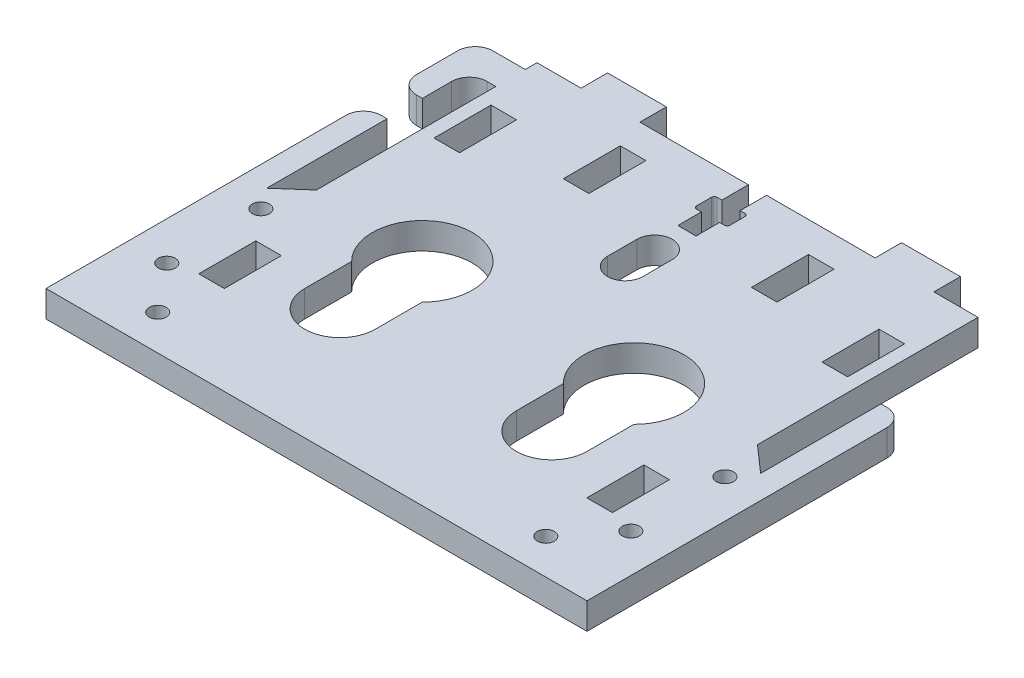
SolidWorks part; units mm, degrees
ref_plane "Front Plane" through (0, 0, 0) normal (0, 0, 1) x (1, 0, 0)
ref_plane "Top Plane" through (0, 0, 0) normal (0, 1, 0) x (1, 0, 0)
ref_plane "Right Plane" through (0, 0, 0) normal (1, 0, 0) x (0, 0, -1)
sketch "Sketch1" plane through (0, 0, 0) normal (0, 1, 0) x (1, 0, 0)
  line L1 (-37.5, 37.5) -> (37.5, 37.5)
  line L2 (-37.5, 37.5) -> (-37.5, -37.5)
  line L3 (-37.5, -37.5) -> (37.5, -37.5)
  line L4 (37.5, 37.5) -> (37.5, -37.5)
  line L5 (-37.5, 37.5) -> (37.5, -37.5) construction
  line L6 (-37.5, -37.5) -> (37.5, 37.5) construction
  point P0 (0, 0)
  dimension "D1" = 75
  dimension "D2" = 75
extrude "MainShape" add sketch "Sketch1" along normal blind 4.5
sketch "Sketch2" plane through (0, 4.5, 0) normal (0, 1, 0) x (1, 0, 0)
  line L0 (0, -37.5) -> (0, 37.5) construction
  line L1 (-37.5, -37.5) -> (37.5, -37.5) construction
  line L2 (37.5, 37.5) -> (-37.5, 37.5) construction
  line L4 (-5, 42) -> (5, 42)
  line L5 (-5, 42) -> (-5, 33)
  line L6 (-5, 33) -> (5, 33)
  line L7 (5, 42) -> (5, 33)
  line L8 (-5, 42) -> (5, 33) construction
  line L9 (-5, 33) -> (5, 42) construction
  dimension "D1" = 10
  dimension "D2" = 4.5
extrude "Tab1" [suppressed] add sketch "Sketch2" against normal through all
sketch "Sketch4" [suppressed] plane through (0, 4.5, 0) normal (0, 1, 0) x (1, 0, 0)
  line L0 (0, 42) -> (0, -37.5) construction
  line L1 (5, 42) -> (-5, 42) construction
  line L2 (-47.5, -37.5) -> (47.5, -37.5) construction
  line L3 (-40, 37.5) -> (-40, 27) construction
  line L4 (-5, 37.5) -> (-47.5, 37.5) construction
  line L5 (-38.25, 27) -> (-41.75, 27) construction
  line L6 (-41.75, 27) -> (-41.75, 37.5) construction
  line L7 (-38.25, 27) -> (-41.75, 27)
  line L8 (-41.75, 27) -> (-41.75, 29.5)
  line L9 (-41.75, 29.5) -> (-42.75, 29.5)
  line L10 (-43, 29.75) -> (-43, 33.45)
  line L11 (-42.75, 33.7) -> (-41.75, 33.7)
  line L12 (-41.75, 33.7) -> (-41.75, 37.5)
  line L13 (-41.75, 37.5) -> (-38.25, 37.5)
  line L14 (-38.25, 27) -> (-38.25, 37.5) construction
  line L15 (-38.25, 33.7) -> (-38.25, 37.5)
  line L16 (-37.25, 33.7) -> (-38.25, 33.7)
  line L17 (-37, 29.75) -> (-37, 33.45)
  line L18 (-38.25, 29.5) -> (-37.25, 29.5)
  line L19 (-38.25, 27) -> (-38.25, 29.5)
  line L20 (38.25, 27) -> (38.25, 37.5) construction
  line L21 (41.75, 27) -> (41.75, 37.5) construction
  line L22 (38.25, 27) -> (41.75, 27) construction
  line L23 (40, 37.5) -> (40, 27) construction
  line L24 (38.25, 27) -> (38.25, 29.5)
  line L25 (38.25, 29.5) -> (37.25, 29.5)
  line L26 (37, 29.75) -> (37, 33.45)
  line L27 (37.25, 33.7) -> (38.25, 33.7)
  line L28 (38.25, 33.7) -> (38.25, 37.5)
  line L29 (41.75, 37.5) -> (38.25, 37.5)
  line L30 (41.75, 33.7) -> (41.75, 37.5)
  line L31 (42.75, 33.7) -> (41.75, 33.7)
  line L32 (43, 29.75) -> (43, 33.45)
  line L33 (41.75, 29.5) -> (42.75, 29.5)
  line L34 (41.75, 27) -> (41.75, 29.5)
  line L35 (38.25, 27) -> (41.75, 27)
  arc A0 (-42.75, 29.5) -> (-43, 29.75) centre (-42.75, 29.75) cw
  arc A1 (-37, 29.75) -> (-37.25, 29.5) centre (-37.25, 29.75) cw
  arc A2 (-37.25, 33.7) -> (-37, 33.45) centre (-37.25, 33.45) cw
  arc A3 (-43, 33.45) -> (-42.75, 33.7) centre (-42.75, 33.45) cw
  arc A4 (43, 33.45) -> (42.75, 33.7) centre (42.75, 33.45) ccw
  arc A5 (37.25, 33.7) -> (37, 33.45) centre (37.25, 33.45) ccw
  arc A6 (37, 29.75) -> (37.25, 29.5) centre (37.25, 29.75) ccw
  arc A7 (42.75, 29.5) -> (43, 29.75) centre (42.75, 29.75) ccw
  point P24 (-43, 29.5)
  point P27 (-37, 29.5)
  point P30 (-37, 33.7)
  point P33 (-43, 33.7)
  point P56 (43, 33.7)
  point P57 (37, 33.7)
  point P58 (37, 29.5)
  point P59 (43, 29.5)
  dimension "D7" = 0.5
  dimension "D1" = 11
  dimension "D2" = 1.55
  dimension "D3" = 3.5
  dimension "D4" = 2.85
  dimension "D5" = 8
  dimension "D6" = 40
extrude "Cut-Extrude2" [suppressed] cut sketch "Sketch4" against normal through all
sketch "Sketch5" plane through (0, 4.5, 0) normal (0, 1, 0) x (1, 0, 0)
  line L0 (0, -37.5) -> (0, 37.5) construction
  line L1 (-37.5, -37.5) -> (37.5, -37.5) construction
  line L3 (33, 37.5) -> (33, -37.5) construction
  line L4 (37.5, 37.5) -> (-37.5, 37.5) construction
  line L5 (-33, 37.5) -> (-33, -37.5) construction
  line L6 (30.825, 27.35) -> (35.175, 27.35)
  line L7 (30.825, 27.35) -> (30.825, 17.65)
  line L8 (30.825, 17.65) -> (35.175, 17.65)
  line L9 (35.175, 27.35) -> (35.175, 17.65)
  line L10 (30.825, 27.35) -> (35.175, 17.65) construction
  line L11 (30.825, 17.65) -> (35.175, 27.35) construction
  line L12 (-30.825, 17.65) -> (-35.175, 27.35) construction
  line L13 (-30.825, 27.35) -> (-35.175, 17.65) construction
  line L14 (-35.175, 27.35) -> (-35.175, 17.65)
  line L15 (-30.825, 17.65) -> (-35.175, 17.65)
  line L16 (-30.825, 27.35) -> (-30.825, 17.65)
  line L17 (-30.825, 27.35) -> (-35.175, 27.35)
  line L18 (-37.5, 2.5) -> (37.5, 2.5) construction
  line L19 (-37.5, 37.5) -> (-37.5, -37.5) construction
  line L20 (37.5, -37.5) -> (37.5, 37.5) construction
  line L21 (-30.825, -22.35) -> (-35.175, -12.65) construction
  line L22 (-30.825, -12.65) -> (-35.175, -22.35) construction
  line L23 (30.825, -12.65) -> (35.175, -22.35) construction
  line L24 (30.825, -22.35) -> (35.175, -12.65) construction
  line L25 (-30.825, -22.35) -> (-35.175, -22.35)
  line L26 (-30.825, -22.35) -> (-30.825, -12.65)
  line L27 (-30.825, -12.65) -> (-35.175, -12.65)
  line L28 (-35.175, -22.35) -> (-35.175, -12.65)
  line L29 (35.175, -22.35) -> (35.175, -12.65)
  line L30 (30.825, -12.65) -> (35.175, -12.65)
  line L31 (30.825, -22.35) -> (30.825, -12.65)
  line L32 (30.825, -22.35) -> (35.175, -22.35)
  line L33 (-30.825, 27.35) -> (-35.175, 17.65) construction
  line L34 (-37.5, 37.5) -> (37.5, 37.5) construction
  line L35 (37.5, 37.5) -> (-37.5, 37.5) construction
  point P10 (33, 22.5)
  point P21 (-33, 22.5)
  point P36 (-33, -17.5)
  point P37 (33, -17.5)
  dimension "D1" = 33
  dimension "D2" = 9.7
  dimension "D3" = 4.35
  dimension "D4" = 15
  dimension "D5" = 40
extrude "Cut-Extrude3" cut sketch "Sketch5" against normal through all
sketch "Sketch6" plane through (0, 4.5, 0) normal (0, 1, 0) x (1, 0, 0)
  line L0 (-18, -37.5) -> (-18, 28) construction
  line L1 (-24, -15.5) -> (-24, -7.5208)
  line L3 (-37.5, -15.5) -> (37.5, -15.5) construction
  line L4 (-37.5, 37.5) -> (-37.5, -37.5) construction
  line L5 (37.5, -37.5) -> (37.5, 37.5) construction
  line L6 (37.5, 37.5) -> (-37.5, 37.5) construction
  line L7 (-37.5, -37.5) -> (37.5, -37.5) construction
  line L8 (-12, -15.5) -> (-12, -7.5208)
  line L9 (-37.5, 37.5) -> (37.5, 37.5) construction
  arc A0 (-24, -15.5) -> (-12, -15.5) centre (-18, -15.5) ccw
  arc A2 (-12, -7.5208) -> (-24, -7.5208) centre (-18, -1.5) ccw
  dimension "D1" = 12
  dimension "D6" = 8.5
  dimension "D2" = 53
  dimension "D3" = 0
  dimension "D5" = 0
  dimension "D7" = 14
  dimension "D4" = 18
extrude "Cut-Extrude4" cut sketch "Sketch6" against normal through all
sketch "Sketch13" plane through (0, 4.5, 0) normal (0, 1, 0) x (1, 0, 0)
  line L0 (-37.5, 0) -> (-46, -7.5)
  line L1 (-37.5, 37.5) -> (-37.5, -37.5) construction
  line L2 (-46, -7.5) -> (-46, -37.5)
  line L3 (-46, -37.5) -> (-37.5, -37.5)
  line L4 (-37.5, -37.5) -> (-37.5, 0)
  line L5 (0, 37.5) -> (0, -37.5) construction
  line L6 (37.5, 37.5) -> (-37.5, 37.5) construction
  line L7 (-37.5, -37.5) -> (37.5, -37.5) construction
  line L8 (37.5, -37.5) -> (37.5, 0)
  line L9 (46, -37.5) -> (37.5, -37.5)
  line L10 (46, -7.5) -> (46, -37.5)
  line L11 (37.5, 0) -> (46, -7.5)
  line L12 (-37.5, -37.5) -> (-37.5, 0)
  line M23 (37.5, -37.5) -> (37.5, 37.5)
  line M25 (-37.5, 37.5) -> (-37.5, -37.5)
  dimension "D1" = 46
  dimension "D2" = 30
extrude "Boss-Extrude2" add sketch "Sketch13" against normal through all contours L2 L3 L0 M25 | L11 L9 L10 M23 region at (-41.5926, 4.5, 20.5556) region at (41.5926, 4.5, 20.5556)
sketch "Sketch8" plane through (0, 4.5, 0) normal (0, 1, 0) x (1, 0, 0)
  line L0 (-18, -9.5) -> (-18, -21.5) construction
  line L1 (-18, -15.5) -> (-39.46, -15.5) construction
  line L2 (-39.46, -23.5) -> (-39.46, -7.5) construction
  line L3 (-18, -21.5) -> (-18, -9.5) construction
  circle A0 centre (-39.46, -7.5) radius 1.45
  circle A1 centre (-18, -15.5) radius 6 construction
  circle A2 centre (-39.46, -23.5) radius 1.45
  dimension "D3" = 2.9
  dimension "D1" = 0
  dimension "D2" = 8
  dimension "D4" = 21.46
extrude "Cut-Extrude6" cut sketch "Sketch8" against normal through all
mirror "Mirror1" about plane through (0, 0, 0) normal (1, 0, 0) of "Cut-Extrude6", "Cut-Extrude4"
sketch "Sketch11" plane through (0, 4.5, 0) normal (0, 1, 0) x (1, 0, 0)
  line L0 (0, 37.5) -> (0, -37.5) construction
  line L1 (37.5, 37.5) -> (-37.5, 37.5) construction
  line L2 (-46, -37.5) -> (46, -37.5) construction
  line L3 (-25, 42) -> (-25, 37.5) construction
  line L4 (-30, 37.5) -> (-20, 37.5)
  line L5 (-30, 37.5) -> (-30, 42)
  line L6 (-30, 42) -> (-20, 42)
  line L7 (-20, 37.5) -> (-20, 42)
  line L8 (25, 42) -> (25, 37.5) construction
  line L9 (20, 37.5) -> (20, 42)
  line L10 (30, 42) -> (20, 42)
  line L11 (30, 37.5) -> (30, 42)
  line L12 (30, 37.5) -> (20, 37.5)
  dimension "D1" = 10
  dimension "D2" = 4.5
  dimension "D3" = 25
extrude "RearTabs" add sketch "Sketch11" against normal through all
sketch "Sketch12" plane through (0, 4.5, 0) normal (0, 1, 0) x (1, 0, 0)
  line L0 (0, 0) -> (0, 37.5) construction
  line L1 (20, 37.5) -> (-20, 37.5) construction
  line L2 (1.55, 37.5) -> (-1.55, 37.5)
  line L3 (-1.55, 37.5) -> (-1.55, 33)
  line L4 (-1.55, 33) -> (-2.35, 33)
  line L5 (-2.85, 32.5) -> (-2.85, 30)
  line L6 (-2.35, 29.5) -> (-1.55, 29.5)
  line L7 (-1.55, 29.5) -> (-1.55, 25.5)
  line L8 (-1.55, 25.5) -> (1.55, 25.5)
  line L9 (1.55, 29.5) -> (1.55, 25.5)
  line L10 (2.35, 29.5) -> (1.55, 29.5)
  line L11 (2.85, 32.5) -> (2.85, 30)
  line L12 (1.55, 33) -> (2.35, 33)
  line L13 (1.55, 37.5) -> (1.55, 33)
  arc A0 (-2.85, 30) -> (-2.35, 29.5) centre (-2.35, 30) ccw
  arc A1 (-2.35, 33) -> (-2.85, 32.5) centre (-2.35, 32.5) ccw
  arc A2 (2.35, 33) -> (2.85, 32.5) centre (2.35, 32.5) cw
  arc A3 (2.85, 30) -> (2.35, 29.5) centre (2.35, 30) cw
  point P14 (-2.85, 29.5)
  point P17 (-2.85, 33)
  point P25 (0, 25.5)
  point P28 (2.85, 33)
  point P29 (2.85, 29.5)
  dimension "D5" = 8
  dimension "D1" = 12
  dimension "D6" = 0.5
  dimension "D2" = 3.5
  dimension "D3" = 2.85
  dimension "D4" = 1.55
extrude "FrontScrewSlot" cut sketch "Sketch12" against normal through all
sketch "Sketch14" plane through (0, 4.5, 0) normal (0, 1, 0) x (1, 0, 0)
  line L0 (-33, 27.35) -> (-33, -37.5) construction
  line L1 (-30.825, 27.35) -> (-35.175, 27.35) construction
  line L2 (-46, -37.5) -> (46, -37.5) construction
  line L3 (-30, 37.5) -> (-37.5, 37.5) construction
  line L4 (0, 0) -> (0, -37.5) construction
  line L5 (33, 27.35) -> (33, -37.5) construction
  line L6 (-33, 27.35) -> (-33, -37.5) construction
  circle A0 centre (-33, -31.5) radius 1.45
  circle A1 centre (33, -31.5) radius 1.45
  dimension "D2" = 2.9
  dimension "D1" = 69
extrude "BraceScrews" cut sketch "Sketch14" against normal through all
sketch "Sketch15" plane through (0, 4.5, 0) normal (0, 1, 0) x (1, 0, 0)
  line L0 (0, -37.5) -> (0, 25.5) construction
  line L1 (-46, -37.5) -> (46, -37.5) construction
  line L2 (-1.55, 25.5) -> (1.55, 25.5) construction
  line L3 (16, 27.5) -> (-16, 27.5) construction
  line L4 (-1.55, 37.5) -> (-20, 37.5) construction
  line L5 (-18.175, 32.35) -> (-13.825, 32.35)
  line L6 (-18.175, 32.35) -> (-18.175, 22.65)
  line L7 (-18.175, 22.65) -> (-13.825, 22.65)
  line L8 (-13.825, 32.35) -> (-13.825, 22.65)
  line L9 (-18.175, 32.35) -> (-13.825, 22.65) construction
  line L10 (-18.175, 22.65) -> (-13.825, 32.35) construction
  line L11 (18.175, 22.65) -> (13.825, 32.35) construction
  line L12 (18.175, 32.35) -> (13.825, 22.65) construction
  line L13 (13.825, 32.35) -> (13.825, 22.65)
  line L14 (18.175, 22.65) -> (13.825, 22.65)
  line L15 (18.175, 32.35) -> (18.175, 22.65)
  line L16 (18.175, 32.35) -> (13.825, 32.35)
  point P19 (0, 27.5)
  dimension "D1" = 16
  dimension "D2" = 4.35
  dimension "D3" = 9.7
  dimension "D4" = 10
extrude "FanTabs" cut sketch "Sketch15" against normal through all
sketch "Sketch16" plane through (0, 4.5, 0) normal (0, 1, 0) x (1, 0, 0)
  line L0 (0, 0) -> (0, 25.5) construction
  line L1 (-1.55, 25.5) -> (1.55, 25.5) construction
  line L2 (0, 20) -> (0, 15) construction
  line L3 (3, 20) -> (3, 15)
  line L4 (-3, 20) -> (-3, 15)
  arc A0 (3, 20) -> (-3, 20) centre (0, 20) ccw
  arc A1 (-3, 15) -> (3, 15) centre (0, 15) ccw
  point P7 (0, 17.5)
  dimension "D1" = 3
  dimension "D2" = 20
  dimension "D3" = 5
extrude "WiringSlot" cut sketch "Sketch16" against normal through all
sketch "Sketch17" [suppressed] plane through (0, 4.5, 0) normal (0, 1, 0) x (1, 0, 0)
  line L0 (-37.5, 14.5) -> (-37.5, 10.5) construction
  line L3 (-37.5, 37.5) -> (-37.5, 0) construction
  line L4 (-36, 14.5) -> (-36, 10.5)
  line L5 (-39, 14.5) -> (-39, 10.5)
  line L6 (-37.5, 14.5) -> (-37.5, 10.5) construction
  line L7 (-34, 14.5) -> (-34, 10.5)
  line L8 (-41, 14.5) -> (-41, 10.5)
  line L9 (-41, 12.5) -> (-37.5, 12.5) construction
  line L10 (0, 0) -> (0, -12.1805) construction
  arc A0 (-36, 14.5) -> (-39, 14.5) centre (-37.5, 14.5) ccw
  arc A1 (-39, 10.5) -> (-36, 10.5) centre (-37.5, 10.5) ccw
  arc A2 (-34, 14.5) -> (-41, 14.5) centre (-37.5, 14.5) ccw
  arc A3 (-41, 10.5) -> (-34, 10.5) centre (-37.5, 10.5) ccw
  point P4 (-37.5, 12.5)
  point P10 (-37.5, 12.5)
  dimension "D4" = 4
  dimension "D5" = 25
  dimension "D1" = 0
  dimension "D2" = 2
  dimension "D3" = 1.5
extrude "Boss-Extrude3" [suppressed] add sketch "Sketch17" against normal through all
mirror "Mirror2" [suppressed] about plane through (0, 0, 0) normal (1, 0, 0)
sketch "Sketch18" [suppressed] plane through (0, 4.5, 0) normal (0, 1, 0) x (1, 0, 0)
  line L0 (0, -37.5) -> (0, 47.6111) construction
  line L1 (-45, -37.5) -> (45, -37.5) construction
  line L2 (-12, 2) -> (-12, -19.46) construction
  line L3 (-4, -19.46) -> (-20, -19.46) construction
  circle A0 centre (-12, 2) radius 5
  circle A1 centre (-20, -19.46) radius 1.45
  circle A2 centre (-4, -19.46) radius 1.45
  dimension "D2" = 8
  dimension "D4" = 21.46
  dimension "D1" = 2.9
  dimension "D3" = 10
  dimension "D5" = 12
  dimension "D6" = 2
extrude "Cut-Extrude7" [suppressed] cut sketch "Sketch18" against normal through all
mirror "Mirror3" [suppressed] about plane through (0, 0, 0) normal (1, 0, 0)
sketch "Sketch19" [suppressed] plane through (0, 4.5, 0) normal (0, 1, 0) x (1, 0, 0)
  line L0 (-17, 2) -> (-7, 2) construction
  line L1 (-12, 2) -> (-4, 2) construction
  line L2 (-12, 4) -> (-4, 4)
  line L3 (-12, 0) -> (-4, 0)
  line L4 (-12, 7) -> (-12, -3) construction
  line L5 (0, 0) -> (0, 6.8806) construction
  line L6 (12, 7) -> (12, -3) construction
  line L7 (17, 2) -> (7, 2) construction
  line L8 (12, 2) -> (4, 2) construction
  line L9 (12, 4) -> (4, 4)
  line L10 (12, 0) -> (4, 0)
  circle A0 centre (-12, 2) radius 5 construction
  arc A1 (-12, 4) -> (-12, 0) centre (-12, 2) ccw
  arc A2 (-4, 0) -> (-4, 4) centre (-4, 2) ccw
  arc A3 (12, 4) -> (12, 0) centre (12, 2) cw
  arc A4 (4, 0) -> (4, 4) centre (4, 2) cw
  point P6 (-8, 2)
  point P23 (8, 2)
  dimension "D1" = 2
  dimension "D2" = 8
extrude "Cut-Extrude8" [suppressed] cut sketch "Sketch19" against normal through all
sketch "Sketch20" plane through (0, 4.5, 0) normal (0, 1, 0) x (1, 0, 0)
  line L0 (0, 0) -> (0, -37.5) construction
  line L1 (-46, -37.5) -> (46, -37.5) construction
  line L2 (-26.9758, -32.9017) -> (-26.9758, -26.6196)
  line L3 (-26.9758, -26.6196) -> (-6.5592, -26.6196)
  line L4 (-6.5592, -26.6196) -> (-6.5592, 9.4097)
  line L5 (-6.5592, 9.4097) -> (6.5592, 9.4097)
  line L6 (-26.9758, -32.9017) -> (26.9758, -32.9017)
  line L7 (6.5592, -26.6196) -> (6.5592, 9.4097)
  line L8 (26.9758, -26.6196) -> (6.5592, -26.6196)
  line L9 (26.9758, -32.9017) -> (26.9758, -26.6196)
  point P12 (0, -32.9017)
  point P13 (0, 9.4097)
extrude "Cut-Extrude9" [suppressed] cut sketch "Sketch20" against normal through all
sketch "Sketch21" plane through (0, 4.5, 0) normal (0, 1, 0) x (1, 0, 0)
  line L0 (-46, -37.5) -> (-46, 35.5) construction
  line L1 (-37, 35.5) -> (-43, 35.5)
  line L4 (-46, 32.5) -> (-46, 25.5)
  line L5 (-43, 22.5) -> (-42, 22.5)
  line L6 (-42, 22.5) -> (-42, 27.5)
  line L7 (-39, 30.5) -> (-37, 30.5)
  line L9 (-37, 30.5) -> (-37, 35.5)
  line L10 (-30, 37.5) -> (-37.5, 37.5) construction
  line L11 (-37.5, 37.5) -> (-37.5, 0) construction
  arc A0 (-42, 27.5) -> (-39, 30.5) centre (-39, 27.5) cw
  arc A1 (-46, 25.5) -> (-43, 22.5) centre (-43, 25.5) ccw
  arc A2 (-43, 35.5) -> (-46, 32.5) centre (-43, 32.5) ccw
  point P19 (-46, 22.5)
  point P24 (-42, 37.5)
  dimension "D1" = 3
  dimension "D4" = 3
  dimension "D2" = 15
  dimension "D3" = 5
  dimension "D5" = 4
  dimension "D6" = 0.5
  dimension "D7" = 2
extrude "Boss-Extrude4" add sketch "Sketch21" against normal through all
sketch "Sketch22" plane through (0, 4.5, 0) normal (0, 1, 0) x (1, 0, 0)
  line L0 (-46, -7.5) -> (-46, 13.5)
  line L1 (-43, 16.5) -> (-42, 16.5)
  line L2 (-42, 16.5) -> (-42, -3.9706)
  line L3 (-37.5, 0) -> (-46, -7.5) construction
  line L4 (-42, -3.9706) -> (-46, -7.5)
  line L5 (-46, 16.5) -> (-46, 28.3122) construction
  line L6 (-46, 32.5) -> (-46, 25.5) construction
  line L7 (-42, 22.6875) -> (-42, 12.0504) construction
  line L8 (-42, 22.5) -> (-42, 27.5) construction
  arc A0 (-46, 13.5) -> (-43, 16.5) centre (-43, 13.5) cw
  dimension "D2" = 3
  dimension "D1" = 6
extrude "Boss-Extrude5" add sketch "Sketch22" against normal through all
mirror "Mirror6" about plane through (0, 0, 0) normal (1, 0, 0) of "Boss-Extrude5"
equation "\"X-ROD-SPACING\"=45"
equation "\"Y-ROD-SPACING\"=75"
equation "\"Z-ROD-SPACING\"=17.5"
equation "\"Y-BED-OFFSET\"=2"
equation "\"Y-BED-ROD-INSET\"=3.5"
equation "\"Y-BED-SCREW-SPACING\"=209"
equation "\"Y-BED-SCREW-CUTOUT-SLOT-HEIGHT\"=2"
equation "\"T-SLOT-NUT-FILLET-RADIUS\"=0.5"
equation "\"T-SLOT-SCREW-SHAFT-RADIUS\"=1.55"
equation "\"T-SLOT-SCREW-SHAFT-CUTOUT-LENGTH\"=11"
equation "\"T-SLOT-NUT-DEPTH\"=3.5"
equation "\"T-SLOT-NUT-WIDTH\"=2.85"
equation "\"T-SLOT-NUT-END-DISTANCE\"=8"
equation "\"ACRYLIC-THICKNESS\"=10"
equation "\"ACRYLIC-THICKNESS2\"=4.5"
equation "\"ACRYLIC-TAB-CUTOUT-SIZE\"=\"ACRYLIC-THICKNESS\"+\"ACRYLIC-TAB-TOLERANCE\"*2"
equation "\"ACRYLIC-TAB-WIDTH\"=\"ACRYLIC-THICKNESS\""
equation "\"ACRYLIC-M3-HOLE\"=2.9"
equation "\"SMOOTHROD-CAP-SCREW-DISTANCE\"=20"
equation "\"FRAME-WIDTH-INNER\"=370"
equation "\"NEMA17-HOLE-SPACING\"=31"
equation "\"NEMA17-CENTRAL-CUTOUT\"=22.5"
equation "\"Z-BRACKET-REACH\"=55"
equation "\"Z-ROD-INSET\"=13.5"
equation "\"TOP-BRACKET-SPACING\"=40"
equation "\"SMOOTHROD-X-LENGTH\"=350"
equation "\"SMOOTHROD-Y-LENGTH\"=350"
equation "\"SMOOTHROD-Z-LENGTH\"=350"
equation "\"SMOOTHROD-TIGHTENING-HEADROOM\"=.25"
equation "\"LEADSCREW-Z-LENGTH\"=300"
equation "\"SCREW-LENGTH-FRAME\"=\"ACRYLIC-THICKNESS\" + 10"
equation "\"SCREW-LENGTH-MOTOR\"=\"ACRYLIC-THICKNESS\" + 5"
equation "\"SCREW-LENGTH-EXTRUDER\"=28"
equation "\"SCREW-HEAD-RADIUS\"=6"
equation "\"PRINTED-X-SMOOTHROD-DIAMETER\"=8.8"
equation "\"PRINTED-X-SMOOTHROD-CUTOUT\"=10"
equation "\"PRINTED-X-BASE-HEIGHT\"=10"
equation "\"PRINTED-LM8UU-CUTOUT-SIZE\"=15.5"
equation "\"PRINTED-LM8UU-CUTOUT-LENGTH\"=24.5"
equation "\"PRINTED-X-IDLER-HEIGHT\"=16"
equation "\"PSU-MOUNTING-WIDTH\"=95"
equation "\"PSU-MOUNTING-HEIGHT\"=177"
equation "\"Y-BELT-TO-ROD-DISTANCE\"=20"
equation "\"SPOOL-HOLDER-ROD-SPACING\"=150"
equation "\"ACRYLIC-X-CARRIAGE-WIDTH\"=55"
equation "\"ACRYLIC-X-CARRIAGE-HEIGHT\"=75"
equation "\"ACRYLIC-X-CARRIAGE-SCREW-SPACING-X\"=15"
equation "\"ACRYLIC-X-CARRIAGE-SCREW-SPACING-Y\"=33"
equation "\"ACRYLIC-X-CARRIAGE-CENTER-TAB-SPACING\"=14"
equation "\"D1@MainShape\" = \"ACRYLIC-THICKNESS2\""
equation "\"D1@Sketch2\"=\"ACRYLIC-TAB-WIDTH\""
equation "\"D2@Sketch2\"=\"ACRYLIC-THICKNESS2\""
equation "\"D1@Sketch4\"=\"T-SLOT-SCREW-SHAFT-CUTOUT-LENGTH\""
equation "\"D2@Sketch4\"=\"T-SLOT-SCREW-SHAFT-RADIUS\""
equation "\"D3@Sketch4\"=\"T-SLOT-NUT-DEPTH\""
equation "\"D4@Sketch4\"=\"T-SLOT-NUT-WIDTH\""
equation "\"D5@Sketch4\"=\"T-SLOT-NUT-END-DISTANCE\""
equation "\"D7@Sketch4\"=\"T-SLOT-NUT-FILLET-RADIUS\""
equation "\"ACRYLIC-X-CARRIAGE-EXTRUDER-SHELF-DEPTH\"=\"ACRYLIC-X-CARRIAGE-EXTRUDER-OFFSET\" + 28"
equation "\"ACRYLIC-X-CARRIAGE-LM8UU-CUTOUT-WIDTH\"=24.25"
equation "\"ACRYLIC-X-CARRIAGE-EXTRUDER-BRACE-SPACING\"=23"
equation "\"ACRYLIC-X-CARRIAGE-EXTRUDER-BRACE-TAB-OFFSET\"=20"
equation "\"ACRYLIC-X-CARRIAGE-EXTRUDER-BRACE-HEIGHT\"=35"
equation "\"ACRYLIC-X-CARRIAGE-EXTRUDER-BRACE-SCREW-SPACING\"=22"
equation "\"D2@Sketch5\"=\"ACRYLIC-THICKNESS2-TAB-CUTOUT-HEIGHT\""
equation "\"D3@Sketch5\"=\"ACRYLIC-THICKNESS2-TAB-CUTOUT-WIDTH\""
equation "\"D3@Sketch8\"=\"ACRYLIC-M3-HOLE\""
equation "\"ACRYLIC-X-CARRIAGE-EXTRUDER-ANGLE\"=90"
equation "\"ACRYLIC-X-CARRIAGE-EXTRUDER-OFFSET\"=26"
equation "\"ACRYLIC-TAB-TOLERANCE\"=-.05"
equation "\"ACRYLIC-X-CARRIAGE-DUAL-WIDTH-MULTIPLIER\"=1.65"
equation "\"ACRYLIC-X-CARRIAGE-DUAL-HOTEND-SPACING\"=42"
equation "\"ACRYLIC-X-CARRIAGE-DUAL-WIDTH\"=75"
equation "\"ACRYLIC-X-CARRIAGE-DUAL-HOTEND-SEPARATION\"=36"
equation "\"ACRYLIC-X-CARRIAGE-DUAL-MOUNT-PLATE-DEPTH\"=75"
equation "\"ACRYLIC-X-CARRIAGE-DUAL-MOUNT-BRACE-WIDTH\"=33"
equation "\"D1@Sketch5\"=\"ACRYLIC-X-CARRIAGE-DUAL-MOUNT-BRACE-WIDTH\""
equation "\"ACRYLIC-X-CARRIAGE-DUAL-MOUNT-SCREW-WIDTH\"=40"
equation "\"D6@Sketch4\"=\"ACRYLIC-X-CARRIAGE-DUAL-MOUNT-SCREW-WIDTH\""
equation "\"D1@Sketch1\"=\"ACRYLIC-X-CARRIAGE-DUAL-WIDTH\""
equation "\"D2@Sketch1\"=\"ACRYLIC-X-CARRIAGE-DUAL-MOUNT-PLATE-DEPTH\""
equation "\"D4@Sketch6\"=\"ACRYLIC-X-CARRIAGE-DUAL-HOTEND-SEPARATION\"/2"
equation "\"D1@Sketch11\"=\"ACRYLIC-TAB-WIDTH\""
equation "\"D2@Sketch11\"=\"ACRYLIC-THICKNESS2\""
equation "\"D1@Sketch12\"=\"T-SLOT-SCREW-SHAFT-CUTOUT-LENGTH\"+1"
equation "\"D2@Sketch12\"=\"T-SLOT-NUT-DEPTH\""
equation "\"D3@Sketch12\"=\"T-SLOT-NUT-WIDTH\""
equation "\"D4@Sketch12\"=\"T-SLOT-SCREW-SHAFT-RADIUS\""
equation "\"D5@Sketch12\"=\"T-SLOT-NUT-END-DISTANCE\""
equation "\"D6@Sketch12\"=\"T-SLOT-NUT-FILLET-RADIUS\""
equation "\"D2@Sketch14\"=\"ACRYLIC-M3-HOLE\""
equation "\"D2@Sketch15\"=\"ACRYLIC-THICKNESS2-TAB-CUTOUT-WIDTH\""
equation "\"D3@Sketch15\"=\"ACRYLIC-THICKNESS2-TAB-CUTOUT-HEIGHT\""
equation "\"KERF\"=0.075"
equation "\"PRINTED-M3-HOLE\"=3.5"
equation "\"PRINTED-M3-NUT-AF\"=6.25"
equation "\"ACRYLIC-X-CARRIAGE-LM8UU-CUTOUT-HEIGHT\"=11.0"
equation "\"ACRYLIC-X-CARRIAGE-DUAL-FAN-OFFSET\"=52"
equation "\"ACRYLIC-X-CARRIAGE-DUAL-FAN-HEIGHT\"=20"
equation "\"BLOWER-FAN-WIDTH\"=15"
equation "\"ACRYLIC-THICKNESS-TAB-CUTOUT-WIDTH\"=\"ACRYLIC-THICKNESS\"-\"KERF\"*2"
equation "\"ACRYLIC-THICKNESS-TAB-CUTOUT-HEIGHT\"=\"ACRYLIC-TAB-WIDTH\"-\"KERF\"*4"
equation "\"ACRYLIC-THICKNESS2-TAB-CUTOUT-WIDTH\"=\"ACRYLIC-THICKNESS2\"-\"KERF\"*2"
equation "\"ACRYLIC-THICKNESS2-TAB-CUTOUT-HEIGHT\"=\"ACRYLIC-TAB-WIDTH\"-\"KERF\"*4"
equation "\"D1@Sketch18\"=\"ACRYLIC-M3-HOLE\""
